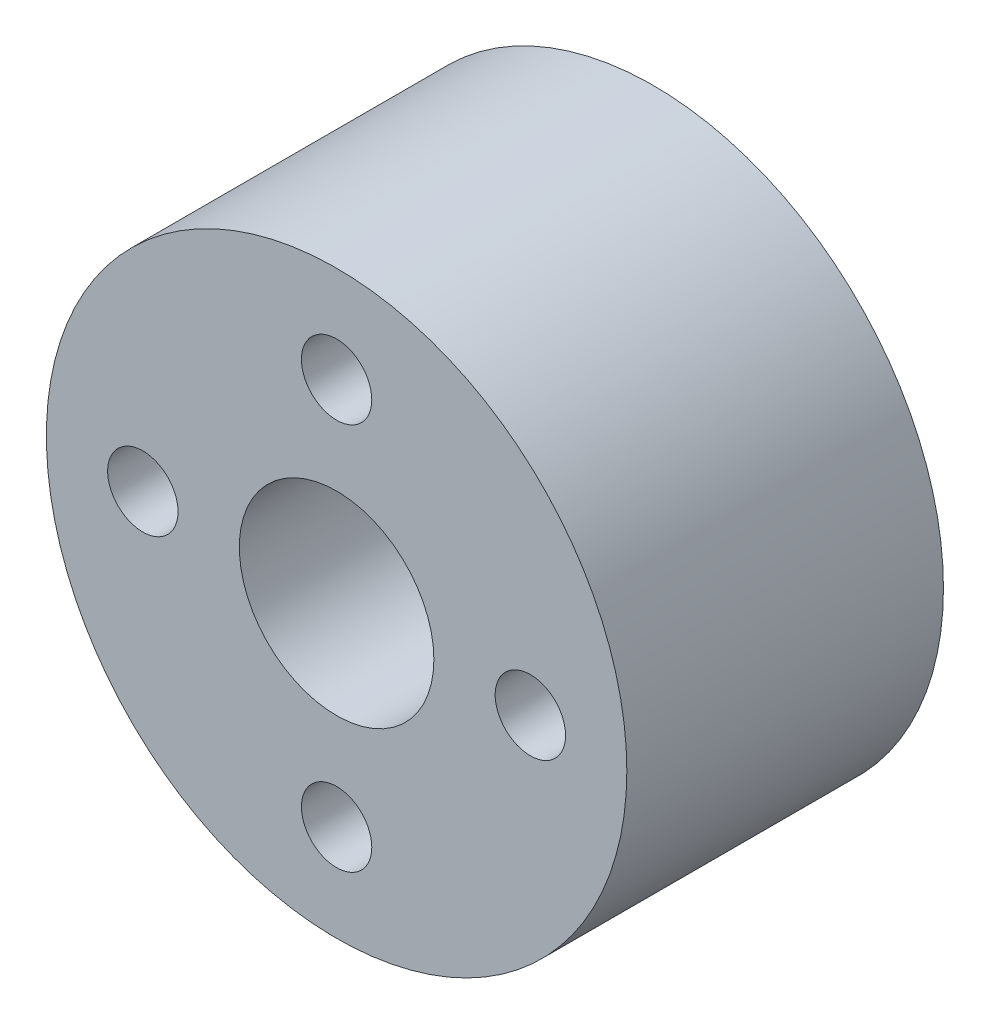
SolidWorks part; units mm, degrees
ref_plane "Front Plane" through (0, 0, 0) normal (0, 0, 1) x (1, 0, 0)
ref_plane "Top Plane" through (0, 0, 0) normal (0, 1, 0) x (1, 0, 0)
ref_plane "Right Plane" through (0, 0, 0) normal (1, 0, 0) x (0, 0, -1)
sketch "Sketch1" plane through (0, 0, 0) normal (0, 0, 1) x (1, 0, 0)
  line L0 (38.1646, 0) -> (38.1646, -88.3733) construction
  line L2 (-55.098, 0) -> (-55.098, -88.3733) construction
  line L3 (-38.1646, 0) -> (-38.1646, -88.3733) construction
  line L4 (8.3909, -46.5555) -> (8.3909, -88.4491) construction
  line L5 (-8.5425, -46.5555) -> (-8.5425, -88.4491) construction
  line L7 (54.9464, 0) -> (54.9464, -88.3733) construction
  line L8 (-69.85, 0) -> (-69.85, -88.3733) construction
  line L9 (69.85, 0) -> (69.85, -88.3733) construction
  line L10 (-23.4126, 0) -> (-23.4126, -88.3733) construction
  line L11 (23.2187, 0) -> (23.2187, -88.3733) construction
  circle A0 centre (0, 0) radius 69.85
  circle A1 centre (0, 0) radius 23.4126
  circle A6 centre (-46.6313, 0) radius 8.4667
  circle A7 centre (0, 46.6313) radius 8.4667
  circle A8 centre (46.6313, 0) radius 8.4667
  circle A9 centre (0, -46.6313) radius 8.4667
  point P17 (-0.0758, 0)
  point P35 (0, 0)
  point P36 (0, 0)
  dimension "D1" = 139.7
  dimension "D2" = 16.9333
  dimension "D3" = 46.8252
  dimension "D4" = 14.752
  dimension "D5" = 14.752
  dimension "D6" = 4
extrude "Boss-Extrude1" add sketch "Sketch1" along normal blind 38.1 and the other way blind 38.1
